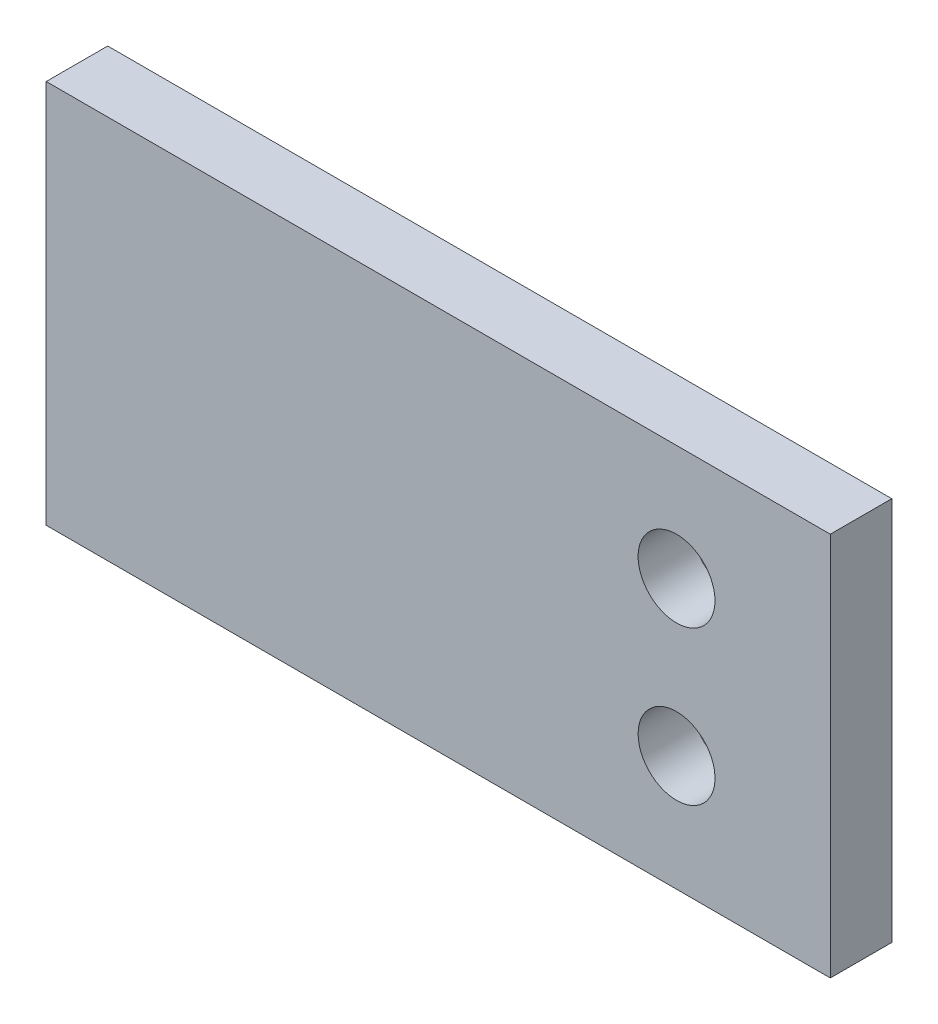
SolidWorks part; units mm, degrees
ref_plane "Front Plane" through (0, 0, 0) normal (0, 0, 1) x (1, 0, 0)
ref_plane "Top Plane" through (0, 0, 0) normal (0, 1, 0) x (1, 0, 0)
ref_plane "Right Plane" through (0, 0, 0) normal (1, 0, 0) x (0, 0, -1)
sketch "Sketch1" plane through (0, 0, 0) normal (0, 0, 1) x (1, 0, 0)
  line L1 (-20, -12.5) -> (20, -12.5)
  line L2 (-20, -12.5) -> (-20, 12.5)
  line L3 (-20, 12.5) -> (20, 12.5)
  line L4 (20, -12.5) -> (20, 12.5)
  line L5 (-20, -12.5) -> (20, 12.5) construction
  line L6 (-20, 12.5) -> (20, -12.5) construction
  point P0 (0, 0)
extrude "Boss-Extrude1" add sketch "Sketch1" along normal blind 4
sketch "Sketch7" plane through (0, 0, 0) normal (0, 0, 1) x (1, 0, 0)
  line L0 (-20, -12.5) -> (20, -12.5) construction
  line L1 (-20, 12.5) -> (-11, 12.5)
  line L2 (-20, 12.5) -> (-20, -12.5)
  line L3 (-20, -12.5) -> (-11, -12.5)
  line L4 (-11, 12.5) -> (-11, -12.5)
extrude "Cut-Extrude5" cut sketch "Sketch7" along normal blind 21
sketch "Sketch8" plane through (0, 0, 0) normal (0, 0, 1) x (1, 0, 0)
  line L1 (20, 12.5) -> (40, 12.5)
  line L2 (20, 12.5) -> (20, -12.5)
  line L3 (20, -12.5) -> (40, -12.5)
  line L4 (40, 12.5) -> (40, -12.5)
extrude "Boss-Extrude2" add sketch "Sketch8" along normal blind 4
sketch "Sketch9" plane through (0, 0, 0) normal (0, 0, 1) x (1, 0, 0)
  circle A0 centre (30, 5) radius 2.5
  circle A1 centre (30, -4.9935) radius 2.5
extrude "Cut-Extrude6" cut sketch "Sketch9" along normal through all both and the other way through all
sketch "Sketch10" plane through (0, 0, 0) normal (0, 0, 1) x (1, 0, 0)
  line L0 (32.5, 0.6699) -> (32.5, -0.6634)
  line L2 (27.5, -0.6634) -> (27.5, 0.6699)
  arc A1 (27.5, -0.6634) -> (32.5, -0.6634) centre (30, -4.9935) ccw
  arc A2 (32.5, 0.6699) -> (27.5, 0.6699) centre (30, 5) ccw
extrude "Cut-Extrude7" cut sketch "Sketch10" along normal blind 0.5 contours A1 L0 A2 L2
fillet "Fillet1" radius 1 4 edges at (27.5, -0.6634, 0.25) (27.5, 0.6699, 0.25) (32.5, -0.6634, 0.25) (32.5, 0.6699, 0.25)
